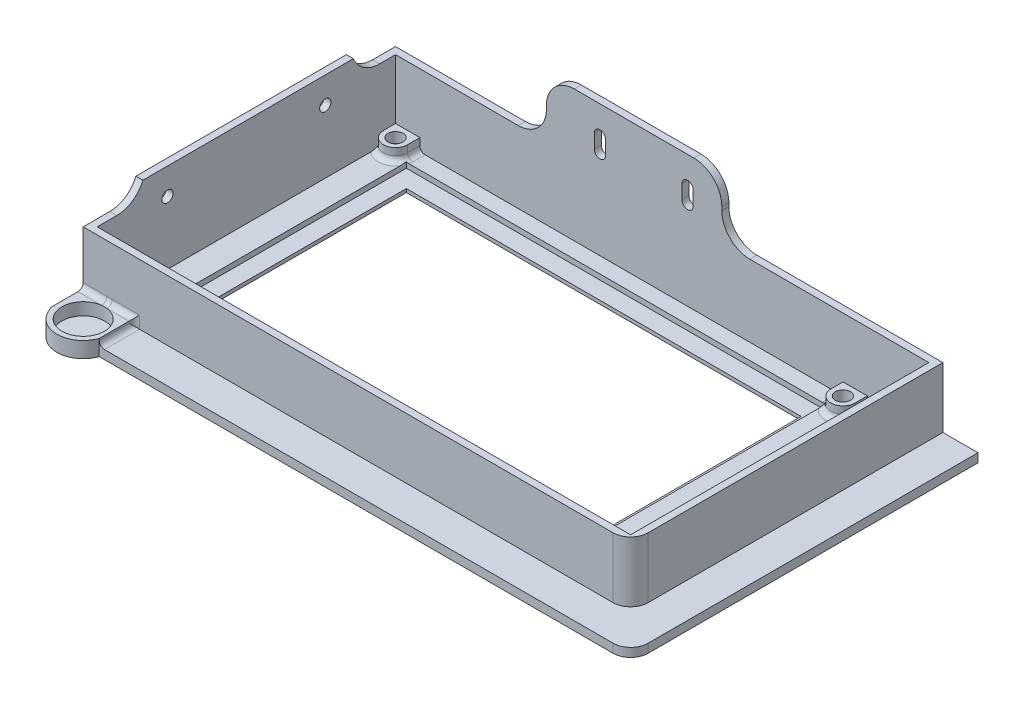
SolidWorks part; units mm, degrees
ref_plane "Alzado" through (0, 0, 0) normal (0, 0, 1) x (1, 0, 0)
ref_plane "Planta" through (0, 0, 0) normal (0, 1, 0) x (1, 0, 0)
ref_plane "Vista lateral" through (0, 0, 0) normal (1, 0, 0) x (0, 0, -1)
sketch "Croquis1" plane through (0, 0, 0) normal (0, 1, 0) x (1, 0, 0)
  line L1 (0, 0) -> (152, 0)
  line L2 (0, 0) -> (0, 85)
  line L3 (0, 85) -> (152, 85)
  line L4 (152, 0) -> (152, 85)
  dimension "D1" = 152
  dimension "D2" = 85
extrude "Saliente-Extruir1" add sketch "Croquis1" along normal blind 1.5
sketch "Croquis2" plane through (0, 1.5, 0) normal (0, 1, 0) x (1, 0, 0)
  line L0 (154, 87) -> (-2, 87)
  line L1 (-2, 87) -> (-2, -2)
  line L2 (-2, -2) -> (154, -2)
  line L3 (154, -2) -> (154, 87)
  line L4 (0, 85) -> (0, 0)
  line L5 (0, 0) -> (152, 0)
  line L6 (152, 0) -> (152, 85)
  line L7 (152, 85) -> (0, 85)
  line L8 (0, 85) -> (0, 0)
  line L9 (0, 0) -> (152, 0)
  line L10 (152, 0) -> (152, 85)
  line L11 (152, 85) -> (0, 85)
  dimension "D1" = 0
  dimension "D2" = 2
extrude "Saliente-Extruir3" add sketch "Croquis2" against normal up to surface (1.5 mm away) and the other way blind 5 up to face at (76, 0, -42.5)
sketch "Croquis3" plane through (0, 1.5, 0) normal (0, 1, 0) x (1, 0, 0)
  line L0 (0, 85) -> (0, 0) construction
  line L1 (152, 85) -> (0, 85) construction
  line L2 (76, 85) -> (76, 0) construction
  line L3 (0, 0) -> (152, 0) construction
  line L4 (0, 42.5) -> (152, 42.5) construction
  line L5 (0, 85) -> (0, 0) construction
  line L6 (152, 0) -> (152, 85) construction
  line L7 (0, 0) -> (152, 0) construction
  circle A0 centre (3.5, 81.5) radius 2.75
  circle A3 centre (3.5, 3.5) radius 3.45
  circle A4 centre (131, 81.5) radius 3.45
  circle A5 centre (131, 3.5) radius 3.45
  circle A6 centre (148.4, 3.5) radius 3.45
  circle A7 centre (148.4, 81.5) radius 3.45
  dimension "D1" = 5.5
  dimension "D4" = 6.9
  dimension "D2" = 3.5
  dimension "D3" = 3.5
  dimension "D5" = 127.5
  dimension "D6" = 3.5
  dimension "D7" = 3.5
  dimension "D8" = 3.5
  dimension "D9" = 3.5
  dimension "D10" = 127.5
  dimension "D11" = 3.6
extrude "Saliente-Extruir4" add sketch "Croquis3" along normal blind 3.5
sketch "Croquis4" plane through (0, 0, 0) normal (0, -1, 0) x (1, 0, 0)
  line L0 (-2, -87) -> (-2, 2) construction
  line L1 (7.6, -80.5) -> (127.1, -80.5)
  line L2 (7.6, -80.5) -> (7.6, -2)
  line L3 (7.6, -2) -> (127.1, -2)
  line L4 (127.1, -80.5) -> (127.1, -2)
  line L5 (154, -87) -> (-2, -87) construction
  dimension "D1" = 119.5
  dimension "D2" = 78.5
  dimension "D3" = 9.6
  dimension "D4" = 6.5
extrude "Cortar-Extruir1" cut sketch "Croquis4" against normal up to surface (1.5 mm away) up to face at (148.4, 1.5, -84.95)
sketch "Croquis5" plane through (0, 5, 0) normal (0, 1, 0) x (1, 0, 0)
  circle A0 centre (131, 3.5) radius 2.15
  circle A1 centre (3.5, 3.5) radius 2.15
  circle A2 centre (3.5, 81.5) radius 2.15
  circle A3 centre (131, 81.5) radius 2.15
  circle A4 centre (148.4, 3.5) radius 2.15
  circle A5 centre (148.4, 81.5) radius 2.15
  dimension "D1" = 4.3
extrude "Cortar-Extruir2" cut sketch "Croquis5" against normal blind 3
sketch "Croquis7" plane through (0, 6.5, 0) normal (0, 1, 0) x (1, 0, 0)
  line L0 (-2, -2) -> (154, -2) construction
  line L1 (0, 0) -> (152, 0) construction
  line L2 (0, 85) -> (0, 0) construction
  line L3 (-2, 87) -> (-2, -2) construction
  line L4 (152, 85) -> (0, 85) construction
  line L5 (154, 87) -> (-2, 87) construction
  line L6 (154, -2) -> (154, 87) construction
  line L7 (152, 0) -> (152, 85) construction
  line L8 (-2, -2) -> (86, -2)
  line L9 (0, 0) -> (86, 0)
  line L10 (0, 85) -> (0, 0)
  line L11 (-2, 87) -> (-2, -2)
  line L12 (152, 85) -> (0, 85)
  line L13 (154, 87) -> (-2, 87)
  line L14 (154, -2) -> (154, 87)
  line L15 (152, 0) -> (152, 85)
  line L16 (86, -2) -> (154, -2)
  line L21 (86, 0) -> (152, 0)
extrude "Saliente-Extruir5" add sketch "Croquis7" along normal blind 15.5
sketch "Croquis9" plane through (0, 22, 0) normal (0, 1, 0) x (1, 0, 0)
  line L0 (152, 85) -> (0, 85) construction
  line L1 (93, 85) -> (43, 85)
  line L2 (93, 85) -> (93, 87)
  line L3 (93, 87) -> (43, 87)
  line L4 (43, 85) -> (43, 87)
  line L5 (154, 87) -> (-2, 87) construction
  dimension "D1" = 50
  dimension "D2" = 45
extrude "Saliente-Extruir6" add sketch "Croquis9" along normal blind 17
sketch "Croquis10" plane through (0, 22, 0) normal (0, 1, 0) x (1, 0, 0)
  line L0 (0, 85) -> (0, 0) construction
  line L1 (0, 13) -> (-2, 13)
  line L2 (0, 13) -> (0, 73)
  line L3 (0, 73) -> (-2, 73)
  line L4 (-2, 13) -> (-2, 73)
  line L5 (-2, 87) -> (-2, -2) construction
  line L6 (-2, -2) -> (154, -2) construction
  dimension "D1" = 60
  dimension "D2" = 15
extrude "Saliente-Extruir7" add sketch "Croquis10" along normal blind 5
sketch "Croquis11" plane through (0, 0, 0) normal (1, 0, 0) x (0, 0, -1)
  line L0 (0, 22) -> (0, 1.5) construction
  line L1 (13, 27) -> (73, 27) construction
  circle A0 centre (20, 19.5) radius 1.6
  circle A1 centre (65, 19.5) radius 1.6
  dimension "D1" = 3.2
  dimension "D2" = 45
  dimension "D3" = 20
  dimension "D4" = 7.5
extrude "Cortar-Extruir4" cut sketch "Croquis11" against normal up to surface (2 mm away) up to face at (-2, 17.75, -42.75)
sketch "Croquis12" plane through (0, 0, -85) normal (0, 0, 1) x (1, 0, 0)
  line L0 (93, 39) -> (93, 22) construction
  line L2 (43, 39) -> (93, 39) construction
  circle A0 centre (83.25, 29) radius 1.6
  circle A1 centre (58.25, 29) radius 1.6
  dimension "D2" = 3.2
  dimension "D1" = 10
  dimension "D3" = 9.75
  dimension "D4" = 25
extrude "Cortar-Extruir5" cut sketch "Croquis12" against normal up to surface (2 mm away) up to face at (72, 20.75, -87)
fillet "Redondeo2" radius 8 6 edges at (-1, 22, -73) (-1, 22, -13) (93, 39, -86) (43, 39, -86) (43, 22, -86) (93, 22, -86)
sketch "Croquis13" plane through (0, 0, 2) normal (0, 0, 1) x (1, 0, 0)
  line L0 (-2, 22) -> (-2, 0) construction
  line L1 (-2, 4.75) -> (154, 4.75)
  line L2 (-2, 4.75) -> (-2, 2.25)
  line L3 (-2, 2.25) -> (154, 2.25)
  line L4 (154, 4.75) -> (154, 2.25)
  line L5 (154, 22) -> (154, 0) construction
  line L6 (-2, 0) -> (154, 0) construction
  dimension "D1" = 2.5
  dimension "D2" = 2.25
extrude "Saliente-Extruir8" add sketch "Croquis13" along normal blind 10
sketch "Croquis14" plane through (154, 0, 0) normal (1, 0, 0) x (0, 0, -1)
  line L0 (87, 22) -> (87, 0) construction
  line L1 (-12, 4.75) -> (87, 4.75)
  line L2 (-12, 4.75) -> (-12, 2.25)
  line L3 (-12, 2.25) -> (87, 2.25)
  line L4 (87, 4.75) -> (87, 2.25)
  line L5 (-12, 2.25) -> (-2, 2.25) construction
extrude "Saliente-Extruir9" add sketch "Croquis14" along normal blind 10
fillet "Redondeo3" radius 5 2 edges at (154, 13.375, 2) (164, 3.5, 12)
sketch "Croquis15" plane through (0, 4.75, 0) normal (0, 1, 0) x (1, 0, 0)
  line L4 (-2, -2) -> (149, -2) construction
  line L5 (-2, -12) -> (-2, -2) construction
  circle A0 centre (5.5, -9.5) radius 7.5
  dimension "D1" = 15
extrude "Saliente-Extruir10" add sketch "Croquis15" against normal up to surface (2.5 mm away) up to face at (117.7589, 2.25, -17.4911)
sketch "Croquis16" plane through (0, 4.75, 0) normal (0, 1, 0) x (1, 0, 0)
  arc A1 (-1.5711, -12) -> (12.5711, -12) centre (5.5, -9.5) ccw construction
  arc A3 (-1.5711, -12) -> (12.5711, -12) centre (5.5, -9.5) ccw construction
  circle A4 centre (5.5, -9.5) radius 6.05
  dimension "D1" = 12.1
extrude "Cortar-Extruir6" cut sketch "Croquis16" against normal blind 1.5
sketch "Croquis17" plane through (0, 0, 0) normal (0, -1, 0) x (1, 0, 0)
  line L0 (127.1, -2) -> (7.6, -2) construction
  line L1 (127.1, -80.5) -> (127.1, -2) construction
  line L2 (7.6, -2) -> (7.6, -80.5) construction
  line L3 (7.6, -80.5) -> (127.1, -80.5) construction
  line L4 (154, -87) -> (154, -3)
  line L5 (149, 2) -> (-2, 2)
  line L6 (-2, 2) -> (-2, -87)
  line L7 (-2, -87) -> (154, -87)
  line L8 (154, -87) -> (154, -3)
  line L9 (149, 2) -> (-2, 2)
  line L10 (-2, 2) -> (-2, -87)
  line L11 (-2, -87) -> (154, -87)
  line L12 (7.6, -80.5) -> (127.1, -80.5)
  line L13 (7.6, -2) -> (7.6, -80.5)
  line L14 (127.1, -80.5) -> (127.1, -2)
  line L15 (127.1, -2) -> (7.6, -2)
  arc A1 (154, -3) -> (149, 2) centre (149, -3) ccw
  arc A2 (154, -3) -> (149, 2) centre (149, -3) ccw
  dimension "D1" = 0
extrude "Saliente-Extruir11" add sketch "Croquis17" along normal blind 1
sketch "Croquis18" plane through (0, -1, 0) normal (0, -1, 0) x (1, 0, 0)
  line L0 (7.6, -2) -> (7.6, -80.5) construction
  line L1 (127.1, -80.5) -> (7.6, -80.5)
  line L2 (127.1, -80.5) -> (127.1, -75.5)
  line L3 (127.1, -75.5) -> (7.6, -75.5)
  line L4 (7.6, -80.5) -> (7.6, -75.5)
  line L6 (7.6, -2) -> (12.6, -2)
  line L7 (7.6, -2) -> (7.6, -75.5)
  line L8 (7.6, -75.5) -> (12.6, -75.5)
  line L9 (12.6, -2) -> (12.6, -75.5)
  line L10 (127.1, -2) -> (12.6, -2)
  line L11 (127.1, -2) -> (127.1, -4)
  line L12 (127.1, -4) -> (12.6, -4)
  line L13 (12.6, -2) -> (12.6, -4)
  line L14 (127.1, -4) -> (125.1, -4)
  line L15 (127.1, -4) -> (127.1, -75.5)
  line L16 (127.1, -75.5) -> (125.1, -75.5)
  line L17 (125.1, -4) -> (125.1, -75.5)
  line M11 (7.6, -80.5) -> (7.6, -2)
  line M12 (7.6, -2) -> (127.1, -2)
  line M13 (127.1, -2) -> (127.1, -80.5)
  line M14 (127.1, -80.5) -> (7.6, -80.5)
  dimension "D1" = 5
  dimension "D2" = 5
  dimension "D3" = 2
  dimension "D4" = 2
extrude "Saliente-Extruir12" add sketch "Croquis18" against normal blind 1 contours L12 L9 M13 M12 | L12 L17 L3 M13 | L3 M13 M11 M14 | L9 L3 M12 M11 region at (67.35, -1, -78) region at (126.1, -1, -39.75) region at (10.1, -1, -38.75) region at (69.85, -1, -3)
sketch "Croquis20" plane through (0, 1.5, 0) normal (0, 1, 0) x (1, 0, 0)
  circle A0 centre (3.5, 81.5) radius 2.75 construction
  circle A1 centre (3.5, 81.5) radius 2.75
  circle A2 centre (3.5, 81.5) radius 3.45
  dimension "D1" = 6.9
extrude "Saliente-Extruir19" add sketch "Croquis20" along normal up to surface (3.5 mm away) up to face at (3.5, 5, -79.35)
sketch "Croquis21" plane through (0, 1.5, 0) normal (0, 1, 0) x (1, 0, 0)
  line L0 (35, 85) -> (0, 85) construction
  line L1 (0, 85) -> (0, 80.4162) construction
  line L2 (6.95, 85) -> (0, 85)
  line L3 (0, 85) -> (0, 81.5)
  line L5 (6.95, 81.5) -> (6.95, 85)
  line L6 (0, 0) -> (152, 0) construction
  line L7 (0, 5.5838) -> (0, 0) construction
  line L8 (0, 0) -> (6.95, 0)
  line L9 (0, 3.5) -> (0, 0)
  line L10 (6.95, 3.5) -> (6.95, 0)
  line L11 (0.05, 3.5) -> (0, 3.5)
  line L12 (0.05, 81.5) -> (0, 81.5)
  circle A1 centre (3.5, 81.5) radius 3.45 construction
  arc A2 (6.95, 81.5) -> (0.05, 81.5) centre (3.5, 81.5) ccw
  circle A3 centre (3.5, 3.5) radius 3.45 construction
  arc A4 (0.05, 3.5) -> (6.95, 3.5) centre (3.5, 3.5) ccw
extrude "Saliente-Extruir20" add sketch "Croquis21" along normal up to surface (3.5 mm away) up to face at (3.5, 5, -1.35)
sketch "Croquis22" plane through (0, 1.5, 0) normal (0, 1, 0) x (1, 0, 0)
  line L0 (134.45, 3.5) -> (134.45, 0)
  line L1 (0, 0) -> (152, 0) construction
  line L2 (134.45, 0) -> (127.55, 0)
  line L4 (127.55, 3.5) -> (127.55, 0)
  line L5 (134.45, 81.5) -> (134.45, 85)
  line L6 (152, 85) -> (101, 85) construction
  line L7 (134.45, 85) -> (127.55, 85)
  line L8 (127.55, 85) -> (127.55, 81.5)
  circle A0 centre (131, 3.5) radius 3.45 construction
  circle A1 centre (131, 3.5) radius 3.45 construction
  arc A2 (127.55, 3.5) -> (134.45, 3.5) centre (131, 3.5) ccw
  circle A3 centre (131, 81.5) radius 3.45 construction
  circle A4 centre (131, 81.5) radius 3.45 construction
  arc A5 (134.45, 81.5) -> (127.55, 81.5) centre (131, 81.5) ccw
extrude "Saliente-Extruir21" add sketch "Croquis22" along normal up to surface (3.5 mm away) up to face at (131, 5, -1.35)
fillet "Redondeo4" radius 1.5 12 edges at (127.55, 1.5, -83.25) (134.45, 1.5, -83.25) (6.95, 1.5, -83.25) (6.95, 1.5, -1.75) (134.45, 1.5, -1.75) (127.55, 1.5, -1.75) (148.4, 1.5, -84.95) (148.4, 1.5, -6.95) (131, 1.5, -78.05) (3.5, 1.5, -78.05) (3.5, 1.5, -6.95) (131, 1.5, -6.95)
sketch "Croquis23" plane through (0, 0, -87) normal (0, 0, -1) x (-1, 0, 0)
  line L0 (-83.25, 27) -> (-83.25, 31) construction
  line L1 (-84.85, 27) -> (-84.85, 31)
  line L2 (-81.65, 27) -> (-81.65, 31)
  line L3 (-58.25, 27) -> (-58.25, 31) construction
  line L4 (-59.85, 27) -> (-59.85, 31)
  line L5 (-56.65, 27) -> (-56.65, 31)
  arc A0 (-84.85, 27) -> (-81.65, 27) centre (-83.25, 27) ccw
  arc A1 (-81.65, 31) -> (-84.85, 31) centre (-83.25, 31) ccw
  arc A2 (-59.85, 27) -> (-56.65, 27) centre (-58.25, 27) ccw
  arc A3 (-56.65, 31) -> (-59.85, 31) centre (-58.25, 31) ccw
  circle A4 centre (-83.25, 29) radius 1.6 construction
  circle A5 centre (-58.25, 29) radius 1.6 construction
  point P2 (-83.25, 29)
  point P9 (-58.25, 29)
  dimension "D1" = 2
  dimension "D2" = 2
extrude "Cortar-Extruir7" cut sketch "Croquis23" against normal up to surface (2 mm away) up to face at (84.85, 29, -85)
sketch "Croquis24" plane through (0, 4.75, 0) normal (0, 1, 0) x (1, 0, 0)
  line L1 (-2, -2) -> (149, -2) construction
  line L2 (-2, -12) -> (-2, -2) construction
  line L3 (-1.5711, -12) -> (-2, -12) construction
  line L5 (-2, -2) -> (12.5711, -2)
  line L6 (-2, -12) -> (-2, -2)
  line L7 (-1.5711, -12) -> (-2, -12)
  line L8 (12.5711, -12) -> (12.5711, -2)
  arc A0 (-1.5711, -12) -> (12.5711, -12) centre (5.5, -9.5) ccw construction
  arc A1 (-1.5711, -12) -> (12.5711, -12) centre (5.5, -9.5) ccw
  circle A2 centre (5.5, -9.5) radius 6.05 construction
  circle A3 centre (5.5, -9.5) radius 6.05
extrude "Saliente-Extruir22" add sketch "Croquis24" along normal blind 2
fillet "Redondeo5" radius 1.5 3 edges at (5.2855, 6.75, 2) (12.5711, 5.75, 2) (12.5711, 4.75, 7)
fillet "Redondeo6" radius 2 1 edges at (-2, 4.5, 12)
